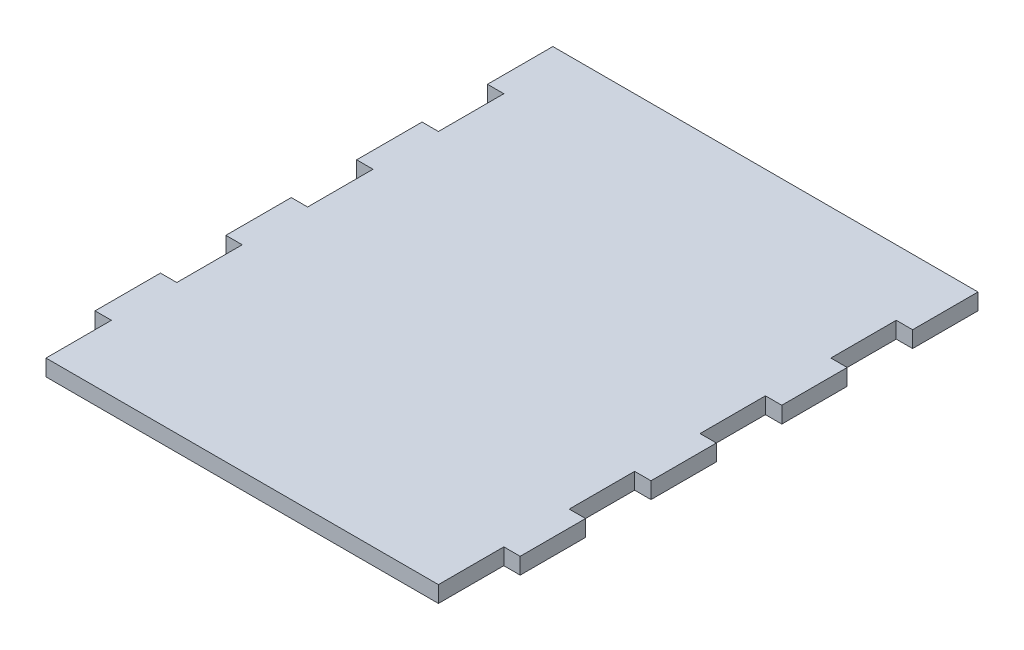
SolidWorks part; units mm, degrees
ref_plane "Front Plane" through (0, 0, 0) normal (0, 0, 1) x (1, 0, 0)
ref_plane "Top Plane" through (0, 0, 0) normal (0, 1, 0) x (1, 0, 0)
ref_plane "Right Plane" through (0, 0, 0) normal (1, 0, 0) x (0, 0, -1)
sketch "Sketch1" plane through (0, 0, 0) normal (0, 1, 0) x (1, 0, 0)
  line L0 (0, 0) -> (76.2, 0)
  line L1 (76.2, 12.7) -> (79.375, 12.7)
  line L2 (79.375, 12.7) -> (79.375, 25.4)
  line L3 (79.375, 25.4) -> (76.2, 25.4)
  line L4 (76.2, 25.4) -> (76.2, 38.1)
  line L5 (76.2, 38.1) -> (79.375, 38.1)
  line L6 (79.375, 38.1) -> (79.375, 50.8)
  line L7 (79.375, 50.8) -> (76.2, 50.8)
  line L8 (76.2, 50.8) -> (76.2, 63.5)
  line L9 (76.2, 63.5) -> (79.375, 63.5)
  line L10 (79.375, 63.5) -> (79.375, 76.2)
  line L11 (79.375, 76.2) -> (76.2, 76.2)
  line L12 (76.2, 76.2) -> (76.2, 88.9)
  line L13 (76.2, 88.9) -> (79.375, 88.9)
  line L14 (79.375, 88.9) -> (79.375, 101.6)
  line L15 (79.375, 101.6) -> (-3.175, 101.6)
  line L16 (-3.175, 101.6) -> (-3.175, 88.9)
  line L17 (-3.175, 88.9) -> (0, 88.9)
  line L18 (0, 88.9) -> (0, 76.2)
  line L19 (0, 76.2) -> (-3.175, 76.2)
  line L20 (-3.175, 76.2) -> (-3.175, 63.5)
  line L21 (-3.175, 63.5) -> (0, 63.5)
  line L22 (0, 63.5) -> (0, 50.8)
  line L23 (0, 50.8) -> (-3.175, 50.8)
  line L24 (-3.175, 50.8) -> (-3.175, 38.1)
  line L25 (-3.175, 38.1) -> (0, 38.1)
  line L26 (0, 38.1) -> (0, 25.4)
  line L27 (0, 25.4) -> (-3.175, 25.4)
  line L28 (-3.175, 25.4) -> (-3.175, 12.7)
  line L29 (-3.175, 12.7) -> (0, 12.7)
  line L30 (0, 12.7) -> (0, 0)
  line L31 (76.2, 12.7) -> (76.2, 0)
  line L32 (38.1, 0) -> (38.1, 101.6) construction
  dimension "D1" = 38.1
  dimension "D2" = 12.7
  dimension "D3" = 3.175
extrude "Boss-Extrude1" add sketch "Sketch1" along normal blind 3.175
